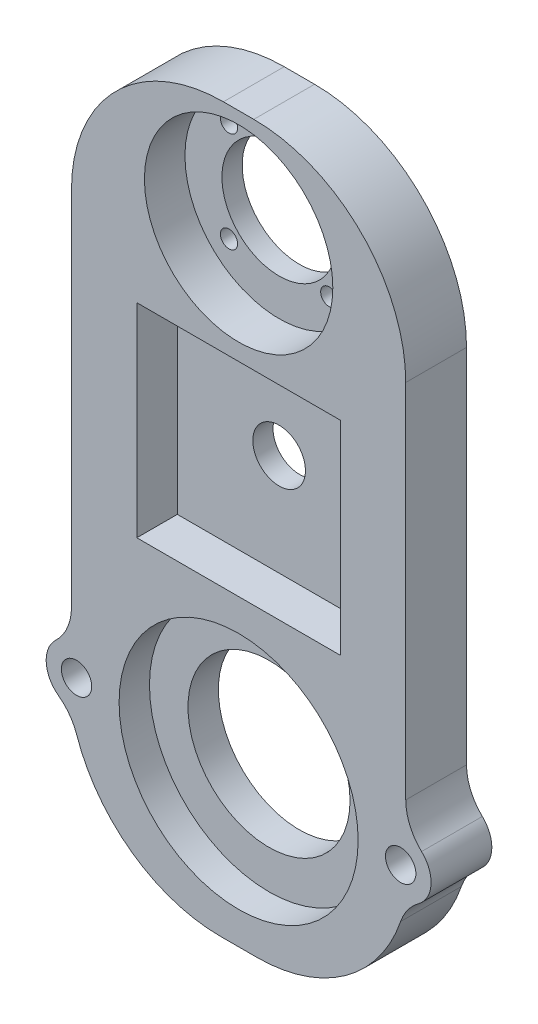
SolidWorks part; units mm, degrees
ref_plane "Front" through (0, 0, 0) normal (0, 0, 1) x (1, 0, 0)
ref_plane "Top" through (0, 0, 0) normal (0, 1, 0) x (1, 0, 0)
ref_plane "Right" through (0, 0, 0) normal (1, 0, 0) x (0, 0, -1)
sketch "Sketch1" plane through (0, 0, 0) normal (0, 0, 1) x (1, 0, 0)
  line L0 (-32, 0) -> (32, 0) construction
  line L1 (-33, 113) -> (33, 113)
  line L2 (-33, 113) -> (-33, -30)
  line L3 (-33, -30) -> (33, -30)
  line L4 (33, 113) -> (33, -30)
  line L6 (-9.9, 101.9) -> (9.9, 101.9) construction
  line L7 (-9.9, 101.9) -> (-9.9, 82.1) construction
  line L8 (-9.9, 82.1) -> (9.9, 82.1) construction
  line L9 (9.9, 101.9) -> (9.9, 82.1) construction
  circle A0 centre (0, 0) radius 16
  circle A1 centre (-32, 0) radius 3 construction
  circle A2 centre (32, 0) radius 3 construction
  circle A3 centre (0, 50) radius 5.2
  circle A4 centre (0, 92) radius 11.3
  circle A5 centre (-9.9, 101.9) radius 1.7
  circle A6 centre (9.9, 101.9) radius 1.7
  circle A7 centre (9.9, 82.1) radius 1.7
  circle A8 centre (-9.9, 82.1) radius 1.7
  point P11 (0, 113)
  point P12 (0, 101.9)
  point P21 (-9.9, 92)
  dimension "D1" = 10.4
  dimension "D3" = 32
  dimension "D7" = 6
  dimension "D9" = 22.6
  dimension "D2" = 21
  dimension "D12" = 3.4
  dimension "D4" = 64
  dimension "D5" = 66
  dimension "D6" = 50
  dimension "D8" = 30
  dimension "D10" = 42
  dimension "D11" = 19.8
extrude "Boss-Extrude1" add sketch "Sketch1" along normal blind 12
sketch "Sketch3" plane through (0, 0, 12) normal (0, 0, 1) x (1, 0, 0)
  line L1 (20.1, 70.1) -> (-20.1, 70.1)
  line L2 (20.1, 70.1) -> (20.1, 29.9)
  line L3 (20.1, 29.9) -> (-20.1, 29.9)
  line L4 (-20.1, 70.1) -> (-20.1, 29.9)
  circle A0 centre (0, 92) radius 18.6
  point P4 (-20.1, 50)
  point P6 (0, 29.9)
  dimension "D2" = 37.2
  dimension "D1" = 40.2
extrude "Cut-Extrude1" cut sketch "Sketch3" against normal blind 8
sketch "Sketch4" plane through (0, 0, 12) normal (0, 0, 1) x (1, 0, 0)
  circle A0 centre (0, 0) radius 23.6
  dimension "D1" = 47.2
extrude "Cut-Extrude2" cut sketch "Sketch4" against normal blind 6
sketch "Sketch5" plane through (0, 0, 0) normal (0, 0, 1) x (1, 0, 0)
  circle A0 centre (-32, 0) radius 6
  circle A1 centre (32, 0) radius 6
  circle A2 centre (32, 0) radius 3 construction
  circle A3 centre (-32, 0) radius 3 construction
  circle A4 centre (32, 0) radius 3
  circle A5 centre (-32, 0) radius 3
  dimension "D1" = 12
extrude "Boss-Extrude2" add sketch "Sketch5" along normal up to vertex (12 mm away) contours A0 | A1 up to point (-20.1, 29.9, 12)
extrude "Cut-Extrude3" cut sketch "Sketch5<3>" along normal through all contours A4 | A5
sketch "Sketch5<3>" plane through (0, 0, 0) normal (0, 0, 1) x (1, 0, 0) same geometry as "Sketch5"
fillet "Fillet1" radius 30 4 edges at (33, -30, 6) (-33, -30, 6) (33, 113, 6) (-33, 113, 6)
fillet "Verrundung1" radius 10 4 edges at (-33, 5.9161, 6) (-33, -5.9161, 6) (33, 5.9161, 6) (33, -5.9161, 6)
